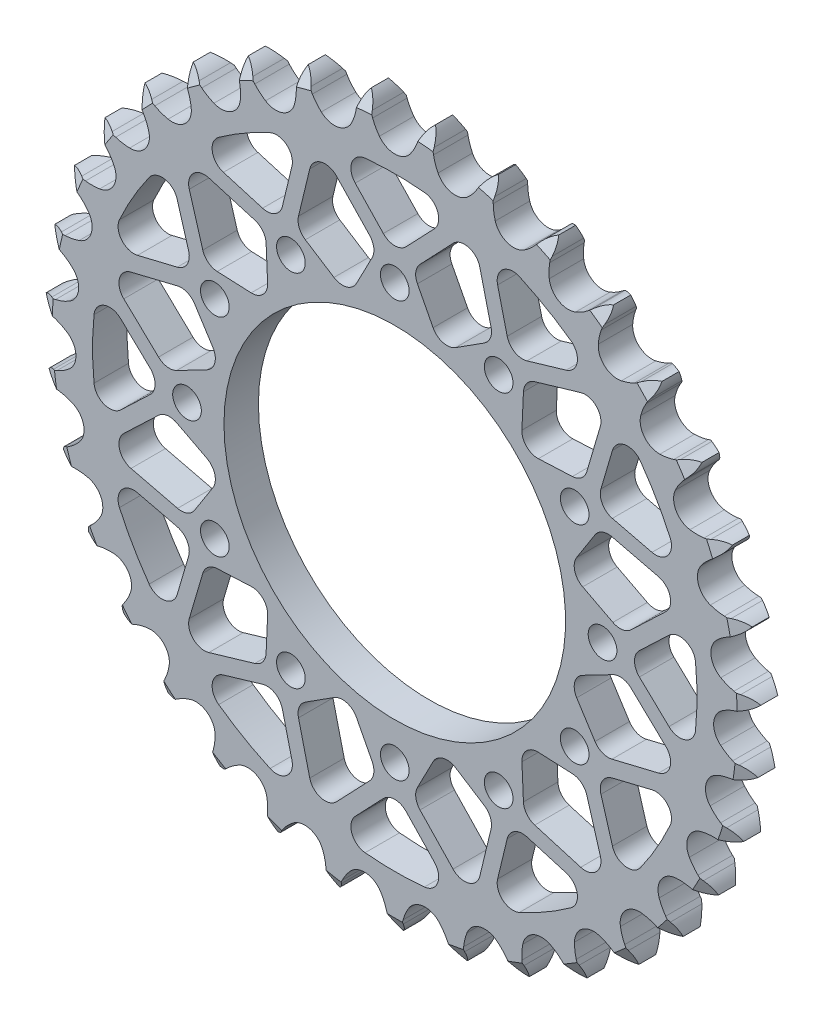
SolidWorks part; units mm, degrees
material "7075-T6 (SN)"
ref_plane "Front Plane" through (0, 0, 0) normal (0, 0, 1) x (1, 0, 0)
ref_plane "Top Plane" through (0, 0, 0) normal (0, 1, 0) x (1, 0, 0)
ref_plane "Right Plane" through (0, 0, 0) normal (1, 0, 0) x (0, 0, -1)
sketch "Work Sketch" plane through (0, 0, 0) normal (0, 0, 1) x (1, 0, 0)
  line L0 (0, 0) -> (0, 160.4542) construction
  line L1 (-112.0919, 70.8395) -> (87.2579, 70.8395) construction
  line L2 (5.0903, 120.8822) -> (5.0903, 112.9699) construction
  line L3 (-12.8497, 74.6356) -> (16.7256, 74.6356) construction
  line L4 (5.0903, 74.6356) -> (-6.074, 66.3097) construction
  line L5 (5.0903, 74.6356) -> (-4.641, 71.0332) construction
  line L6 (-4.641, 71.0332) -> (-6.9559, 77.2865)
  line L7 (-11.5114, 69.8433) -> (-7.1525, 69.8433) construction
  line L8 (-11.0678, 124.7602) -> (-11.0678, 110.2345) construction
  line L9 (0, 0) -> (-3.8324, 42.5811) construction
  circle A0 centre (0, 0) radius 70.8395
  circle A1 centre (0, 70.8395) radius 4.0088
  arc A2 (-4.641, 71.0332) -> (-3.2136, 68.4429) centre (5.0682, 74.6949) ccw
  circle A3 centre (-11.0678, 69.8433) radius 6.4401
  point P23 (-3.2136, 68.4429)
  dimension "D1" = 141.6789
  dimension "D8" = 10.3767
  dimension "D2" = 8.0177
  dimension "D3" = 5.0903
  dimension "D4" = 3.7962
  dimension "D5" = 36.714
  dimension "D6" = 16.4
  dimension "D7" = 10.3767
  dimension "D9" = 0.9961
  dimension "D10" = 11.0678
  dimension "D11" = 5.143
sketch "Teeth Sketch" plane through (0, 0, 0) normal (0, 0, 1) x (1, 0, 0)
  line L0 (5.0282, 72.0792) -> (4.641, 71.0332)
  line L1 (-8.3399, 92.6643) -> (-5.3292, 59.2127) construction
  line L2 (0, 0) -> (-12.1309, 132.2) construction
  line L3 (7.9229, 71.8186) -> (8.1171, 70.7203)
  line L4 (17927.8618, -199194.8588) -> (-17931.6941, 199237.4399) construction
  line L5 (0, 146.3285) -> (0, 56.9858) construction
  line L6 (17.8176, 70.023) -> (17.2498, 69.063)
  line L7 (0, -200000) -> (0, 200160.4542) construction
  line L8 (20.6192, 69.2498) -> (20.6142, 68.1345)
  line L9 (-4.641, 71.0332) -> (-6.9559, 77.2865) construction
  line L10 (43.6371, 57.589) -> (43.2405, 56.5465)
  line L11 (-5.0282, 72.0792) -> (-4.641, 71.0332)
  line L12 (30.0344, 65.7163) -> (29.3043, 64.873)
  line L13 (32.6529, 64.4552) -> (32.4488, 63.3587)
  line L14 (41.2858, 59.2973) -> (40.4169, 58.598)
  line L15 (51.2103, 50.9725) -> (50.2305, 50.4396)
  line L16 (53.2187, 48.8718) -> (52.6424, 47.9169)
  line L17 (59.4888, 41.0094) -> (58.4296, 40.66)
  line L18 (61.0899, 38.5838) -> (60.3523, 37.7472)
  line L19 (65.8553, 29.7283) -> (64.7507, 29.5736)
  line L20 (66.9976, 27.0558) -> (66.1224, 26.3643)
  line L21 (70.1052, 17.4916) -> (68.9907, 17.5366)
  line L22 (70.7519, 14.6581) -> (69.7673, 14.134)
  line L23 (72.1018, 4.6927) -> (71.0133, 4.9361)
  line L24 (72.2322, 1.7893) -> (71.1699, 1.4494)
  line L25 (71.781, -8.2569) -> (70.7534, -7.8232)
  line L26 (71.3909, -11.137) -> (70.2849, -11.2818)
  line L27 (69.1531, -20.9412) -> (68.2195, -20.331)
  line L28 (68.255, -23.7054) -> (67.141, -23.6503)
  line L29 (64.3026, -32.9525) -> (63.493, -32.1853)
  line L30 (62.9254, -35.5118) -> (61.8391, -35.2587)
  line L31 (57.3853, -43.9046) -> (56.7257, -43.0052)
  line L32 (55.5732, -46.1769) -> (54.5496, -45.7339)
  line L33 (48.6237, -53.4456) -> (48.1352, -52.4428)
  line L34 (46.435, -55.3578) -> (45.5069, -54.7392)
  line L35 (38.2992, -61.2688) -> (37.9976, -60.1949)
  line L36 (35.8042, -62.7594) -> (35.0015, -61.985)
  line L37 (26.7437, -67.1227) -> (26.6388, -66.0123)
  line L38 (24.0227, -68.144) -> (23.3712, -67.2387)
  line L39 (14.3287, -70.8193) -> (14.4237, -69.708)
  line L40 (11.4691, -71.3383) -> (10.9896, -70.3312)
  line L41 (1.4532, -72.2397) -> (1.7451, -71.1632)
  line L42 (-1.4532, -72.2397) -> (-1.7451, -71.1632)
  line L43 (-11.4691, -71.3383) -> (-10.9896, -70.3312)
  line L44 (-14.3287, -70.8193) -> (-14.4237, -69.708)
  line L45 (-24.0227, -68.144) -> (-23.3712, -67.2387)
  line L46 (-26.7437, -67.1227) -> (-26.6388, -66.0123)
  line L47 (-35.8042, -62.7594) -> (-35.0015, -61.985)
  line L48 (-38.2992, -61.2688) -> (-37.9976, -60.1949)
  line L49 (-46.435, -55.3578) -> (-45.5069, -54.7392)
  line L50 (-48.6237, -53.4456) -> (-48.1352, -52.4428)
  line L51 (-55.5732, -46.1769) -> (-54.5496, -45.7339)
  line L52 (-57.3853, -43.9046) -> (-56.7257, -43.0052)
  line L53 (-62.9254, -35.5118) -> (-61.8391, -35.2587)
  line L54 (-64.3026, -32.9525) -> (-63.493, -32.1853)
  line L55 (-68.255, -23.7054) -> (-67.141, -23.6503)
  line L56 (-69.1531, -20.9412) -> (-68.2195, -20.331)
  line L57 (-71.3909, -11.137) -> (-70.2849, -11.2818)
  line L58 (-71.781, -8.2569) -> (-70.7534, -7.8232)
  line L59 (-72.2322, 1.7893) -> (-71.1699, 1.4494)
  line L60 (-72.1018, 4.6927) -> (-71.0133, 4.9361)
  line L61 (-70.7519, 14.6581) -> (-69.7673, 14.134)
  line L62 (-70.1052, 17.4916) -> (-68.9907, 17.5366)
  line L63 (-66.9976, 27.0558) -> (-66.1224, 26.3643)
  line L64 (-65.8553, 29.7283) -> (-64.7507, 29.5736)
  line L65 (-61.0899, 38.5838) -> (-60.3523, 37.7472)
  line L66 (-59.4888, 41.0094) -> (-58.4296, 40.66)
  line L67 (-53.2187, 48.8718) -> (-52.6424, 47.9169)
  line L68 (-51.2103, 50.9725) -> (-50.2305, 50.4396)
  line L69 (-43.6371, 57.589) -> (-43.2405, 56.5465)
  line L70 (-41.2858, 59.2973) -> (-40.4169, 58.598)
  line L71 (-32.6529, 64.4552) -> (-32.4488, 63.3587)
  line L72 (-30.0344, 65.7163) -> (-29.3043, 64.873)
  line L73 (-20.6192, 69.2498) -> (-20.6142, 68.1345)
  line L74 (-17.8176, 70.023) -> (-17.2498, 69.063)
  line L75 (-7.9229, 71.8186) -> (-8.1171, 70.7203)
  arc A0 (-6.856, 74.7153) -> (-5.0282, 72.0792) centre (-11.0678, 69.8433) cw
  circle A1 centre (-11.0678, 69.8433) radius 6.4401 construction
  arc A2 (-3.2136, 68.4429) -> (-4.641, 71.0332) centre (5.0682, 74.6949) cw
  arc A3 (-4.641, 71.0332) -> (-3.2136, 68.4429) centre (5.0682, 74.6949) ccw construction
  circle A4 centre (0, 70.8395) radius 4.0088 construction
  arc A5 (-3.2136, 68.4429) -> (3.2136, 68.4429) centre (0, 70.8395) ccw
  arc A6 (3.2136, 68.4429) -> (4.641, 71.0332) centre (-5.0682, 74.6949) ccw
  arc A7 (6.856, 74.7153) -> (5.0282, 72.0792) centre (11.0678, 69.8433) ccw
  arc A8 (6.5951, 74.7388) -> (7.9229, 71.8186) centre (1.5811, 70.6972) cw
  arc A9 (9.059, 67.9168) -> (8.1171, 70.7203) centre (18.324, 72.5896) cw
  arc A10 (9.059, 67.9168) -> (15.3829, 66.7692) centre (12.6489, 69.701) ccw
  arc A11 (15.3829, 66.7692) -> (17.2498, 69.063) centre (8.3506, 74.3995) ccw
  arc A12 (20.0867, 72.2905) -> (17.8176, 70.023) centre (23.3609, 66.7447) ccw
  arc A13 (19.8343, 72.3601) -> (20.6192, 69.2498) centre (14.1792, 69.2787) cw
  arc A14 (21.0404, 65.2078) -> (20.6142, 68.1345) centre (30.9909, 68.1512) cw
  arc A15 (21.0404, 65.2078) -> (27.0578, 62.9494) centre (24.8912, 66.3224) ccw
  arc A16 (27.0578, 62.9494) -> (29.3043, 64.873) centre (21.5009, 71.7128) ccw
  arc A17 (32.6719, 67.5421) -> (30.0344, 65.7163) centre (34.9032, 61.5008) ccw
  arc A18 (32.4359, 67.6557) -> (32.6529, 64.4552) centre (26.3215, 65.6336) cw
  arc A19 (32.3456, 60.403) -> (32.4488, 63.3587) centre (42.6617, 61.5223) cw
  arc A20 (32.3456, 60.403) -> (37.863, 57.1065) centre (36.3335, 60.812) ccw
  arc A21 (37.863, 57.1065) -> (40.4169, 58.598) centre (33.9602, 66.7212) ccw
  arc A22 (44.207, 60.6229) -> (41.2858, 59.2973) centre (45.3237, 54.2803) ccw
  arc A23 (43.9951, 60.7768) -> (43.6371, 57.589) centre (37.6178, 59.8789) cw
  arc A24 (42.6112, 53.6567) -> (43.2405, 56.5465) centre (52.9614, 52.9161) cw
  arc A25 (42.6112, 53.6567) -> (47.4513, 49.428) centre (46.608, 53.3472) ccw
  arc A26 (47.4513, 49.428) -> (50.2305, 50.4396) centre (45.328, 59.5852) ccw
  arc A27 (54.3212, 51.7552) -> (51.2103, 50.9725) centre (54.2875, 45.3151) ccw
  arc A28 (54.1402, 51.9445) -> (53.2187, 48.8718) centre (47.7051, 52.1997) cw
  arc A29 (51.5072, 45.1859) -> (52.6424, 47.9169) centre (61.5588, 42.6091) cw
  arc A30 (51.5072, 45.1859) -> (55.5144, 40.161) centre (55.3845, 44.1677) ccw
  arc A31 (55.5144, 40.161) -> (58.4296, 40.66) centre (55.2389, 50.534) ccw
  arc A32 (62.6894, 41.224) -> (59.4888, 41.0094) centre (61.5064, 34.8935) ccw
  arc A33 (62.5452, 41.4426) -> (61.0899, 38.5838) centre (56.2591, 42.8428) cw
  arc A34 (58.7477, 35.2628) -> (60.3523, 37.7472) centre (68.1777, 30.9326) cw
  arc A35 (58.7477, 35.2628) -> (61.7933, 29.6031) centre (62.3809, 33.5686) ccw
  arc A36 (61.7933, 29.6031) -> (64.7507, 29.5736) centre (63.3744, 39.8586) ccw
  arc A37 (69.0428, 29.3679) -> (65.8553, 29.7283) centre (66.7484, 23.3503) ccw
  arc A38 (68.9399, 29.6087) -> (66.9976, 27.0558) centre (63.0048, 32.1088) cw
  arc A39 (64.1, 24.2063) -> (66.1224, 26.3643) centre (72.6052, 18.2619) cw
  arc A40 (64.1, 24.2063) -> (66.0861, 18.0937) centre (67.3723, 21.8906) ccw
  arc A41 (66.0861, 18.0937) -> (68.9907, 17.5366) centre (69.4729, 27.9021) ccw
  arc A42 (73.1771, 16.5679) -> (70.1052, 17.4916) centre (69.8451, 11.0567) ccw
  arc A43 (73.1188, 16.8232) -> (70.7519, 14.6581) centre (67.7256, 20.3429) cw
  arc A44 (67.3921, 12.3718) -> (69.7673, 14.134) centre (74.6992, 5.0042) cw
  arc A45 (67.3921, 12.3718) -> (68.2548, 6.0028) centre (70.1983, 9.509) ccw
  arc A46 (68.2548, 6.0028) -> (71.0133, 4.9361) centre (73.3386, 15.0489) ccw
  arc A47 (74.9595, 3.2354) -> (72.1018, 4.6927) centre (70.6969, -1.5923) ccw
  arc A48 (74.9477, 3.497) -> (72.2322, 1.7893) centre (70.2696, 7.9231) cw
  arc A49 (68.5181, 0.1397) -> (71.1699, 1.4494) centre (74.3923, -8.4143) cw
  arc A50 (68.5181, 0.1397) -> (68.2298, -6.281) centre (70.7681, -3.1782) ccw
  arc A51 (68.2298, -6.281) -> (70.7534, -7.8232) centre (74.8471, 1.7119) ccw
  arc A52 (74.3325, -10.2012) -> (71.781, -8.2569) centre (69.2765, -14.1901) ccw
  arc A53 (74.3677, -9.9416) -> (71.3909, -11.137) centre (70.555, -4.7513) cw
  arc A54 (67.442, -12.097) -> (70.2849, -11.2818) centre (71.6944, -21.5623) cw
  arc A55 (67.442, -12.097) -> (66.0118, -18.363) centre (69.0634, -15.7633) ccw
  arc A56 (66.0118, -18.363) -> (68.2195, -20.331) centre (73.9499, -11.6801) ccw
  arc A57 (71.3165, -23.3098) -> (69.1531, -20.9412) centre (65.6294, -26.3319) ccw
  arc A58 (71.3974, -23.0607) -> (68.255, -23.7054) centre (68.5728, -17.2731) cw
  arc A59 (64.1981, -23.9448) -> (67.141, -23.6503) centre (66.6921, -34.0173) cw
  arc A60 (64.1981, -23.9448) -> (61.6721, -29.8547) centre (65.1388, -27.8417) ccw
  arc A61 (61.6721, -29.8547) -> (63.493, -32.1853) centre (70.676, -24.6966) ccw
  arc A62 (66.0083, -35.6693) -> (64.3026, -32.9525) centre (59.873, -37.6273) ccw
  arc A63 (66.1324, -35.4386) -> (62.9254, -35.5118) centre (64.3866, -29.2396) cw
  arc A64 (58.8909, -35.023) -> (61.8391, -35.2587) centre (59.5463, -45.379) cw
  arc A65 (58.8909, -35.023) -> (55.3502, -40.3869) centre (59.1207, -39.0252) ccw
  arc A66 (55.3502, -40.3869) -> (56.7257, -43.0052) centre (65.1304, -36.9194) ccw
  arc A67 (58.5785, -46.8823) -> (57.3853, -43.9046) centre (52.1922, -47.7133) ccw
  arc A68 (58.7418, -46.6775) -> (55.5732, -46.1769) centre (58.1309, -40.2664) cw
  arc A69 (51.6909, -44.9755) -> (54.5496, -45.7339) centre (50.4867, -55.2821) cw
  arc A70 (51.6909, -44.9755) -> (47.2494, -49.6211) centre (51.2024, -48.9545) ccw
  arc A71 (47.2494, -49.6211) -> (48.1352, -52.4428) centre (57.4915, -47.9556) ccw
  arc A72 (49.266, -56.5885) -> (48.6237, -53.4456) centre (42.8339, -56.2658) ccw
  arc A73 (49.4632, -56.4161) -> (46.435, -55.3578) centre (50.0069, -49.999) cw
  arc A74 (42.8296, -53.4825) -> (45.5069, -54.7392) centre (39.8043, -63.4085) cw
  arc A75 (42.8296, -53.4825) -> (37.6299, -57.2603) centre (41.6384, -57.3103) ccw
  arc A76 (37.6299, -57.2603) -> (37.9976, -60.1949) centre (48.0048, -57.4505) ccw
  arc A77 (38.37, -64.4758) -> (38.2992, -61.2688) centre (32.0989, -63.0099) ccw
  arc A78 (38.5948, -64.3415) -> (35.8042, -62.7594) centre (40.2756, -58.1246) cw
  arc A79 (32.5916, -60.2706) -> (35.0015, -61.985) centre (27.8426, -69.4968) cw
  arc A80 (32.5916, -60.2706) -> (26.8009, -63.0592) centre (30.7361, -63.8241) ccw
  arc A81 (26.8009, -63.0592) -> (26.6388, -66.0123) centre (36.9752, -65.0988) ccw
  arc A82 (26.2407, -70.2909) -> (26.7437, -67.1227) centre (20.3322, -67.7288) ccw
  arc A83 (26.4859, -70.1989) -> (24.0227, -68.144) centre (29.2498, -64.382) cw
  arc A84 (21.3061, -65.1215) -> (23.3712, -67.2387) centre (14.9861, -73.3515) cw
  arc A85 (21.3061, -65.1215) -> (15.1105, -66.8313) centre (18.8459, -68.2866) ccw
  arc A86 (15.1105, -66.8313) -> (14.4237, -69.708) centre (24.7571, -70.6548) ccw
  arc A87 (13.2681, -73.8468) -> (14.3287, -70.8193) centre (7.912, -70.2708) ccw
  arc A88 (13.5258, -73.8) -> (11.4691, -71.3383) centre (17.2839, -68.5701) cw
  arc A89 (9.3358, -67.8793) -> (10.9896, -70.3312) centre (1.6478, -74.8485) cw
  arc A90 (9.3358, -67.8793) -> (2.9345, -68.4554) centre (6.35, -70.5543) ccw
  arc A91 (2.9345, -68.4554) -> (1.7451, -71.1632) centre (11.7434, -73.9399) ccw
  arc A92 (-0.131, -75.0291) -> (1.4532, -72.2397) centre (-4.7625, -70.5543) ccw
  arc A93 (0.131, -75.0291) -> (-1.4532, -72.2397) centre (4.7625, -70.5543) cw
  arc A94 (-2.9345, -68.4554) -> (-1.7451, -71.1632) centre (-11.7434, -73.9399) cw
  arc A95 (-2.9345, -68.4554) -> (-9.3358, -67.8793) centre (-6.35, -70.5543) ccw
  arc A96 (-9.3358, -67.8793) -> (-10.9896, -70.3312) centre (-1.6478, -74.8485) ccw
  arc A97 (-13.5258, -73.8) -> (-11.4691, -71.3383) centre (-17.2839, -68.5701) ccw
  arc A98 (-13.2681, -73.8468) -> (-14.3287, -70.8193) centre (-7.912, -70.2708) cw
  arc A99 (-15.1105, -66.8313) -> (-14.4237, -69.708) centre (-24.7571, -70.6548) cw
  arc A100 (-15.1105, -66.8313) -> (-21.3061, -65.1215) centre (-18.8459, -68.2866) ccw
  arc A101 (-21.3061, -65.1215) -> (-23.3712, -67.2387) centre (-14.9861, -73.3515) ccw
  arc A102 (-26.4859, -70.1989) -> (-24.0227, -68.144) centre (-29.2498, -64.382) ccw
  arc A103 (-26.2407, -70.2909) -> (-26.7437, -67.1227) centre (-20.3322, -67.7288) cw
  arc A104 (-26.8009, -63.0592) -> (-26.6388, -66.0123) centre (-36.9752, -65.0988) cw
  arc A105 (-26.8009, -63.0592) -> (-32.5916, -60.2706) centre (-30.7361, -63.8241) ccw
  arc A106 (-32.5916, -60.2706) -> (-35.0015, -61.985) centre (-27.8426, -69.4968) ccw
  arc A107 (-38.5948, -64.3415) -> (-35.8042, -62.7594) centre (-40.2756, -58.1246) ccw
  arc A108 (-38.37, -64.4758) -> (-38.2992, -61.2688) centre (-32.0989, -63.0099) cw
  arc A109 (-37.6299, -57.2603) -> (-37.9976, -60.1949) centre (-48.0048, -57.4505) cw
  arc A110 (-37.6299, -57.2603) -> (-42.8296, -53.4825) centre (-41.6384, -57.3103) ccw
  arc A111 (-42.8296, -53.4825) -> (-45.5069, -54.7392) centre (-39.8043, -63.4085) ccw
  arc A112 (-49.4632, -56.4161) -> (-46.435, -55.3578) centre (-50.0069, -49.999) ccw
  arc A113 (-49.266, -56.5885) -> (-48.6237, -53.4456) centre (-42.8339, -56.2658) cw
  arc A114 (-47.2494, -49.6211) -> (-48.1352, -52.4428) centre (-57.4915, -47.9556) cw
  arc A115 (-47.2494, -49.6211) -> (-51.6909, -44.9755) centre (-51.2024, -48.9545) ccw
  arc A116 (-51.6909, -44.9755) -> (-54.5496, -45.7339) centre (-50.4867, -55.2821) ccw
  arc A117 (-58.7418, -46.6775) -> (-55.5732, -46.1769) centre (-58.1309, -40.2664) ccw
  arc A118 (-58.5785, -46.8823) -> (-57.3853, -43.9046) centre (-52.1922, -47.7133) cw
  arc A119 (-55.3502, -40.3869) -> (-56.7257, -43.0052) centre (-65.1304, -36.9194) cw
  arc A120 (-55.3502, -40.3869) -> (-58.8909, -35.023) centre (-59.1207, -39.0252) ccw
  arc A121 (-58.8909, -35.023) -> (-61.8391, -35.2587) centre (-59.5463, -45.379) ccw
  arc A122 (-66.1324, -35.4386) -> (-62.9254, -35.5118) centre (-64.3866, -29.2396) ccw
  arc A123 (-66.0083, -35.6693) -> (-64.3026, -32.9525) centre (-59.873, -37.6273) cw
  arc A124 (-61.6721, -29.8547) -> (-63.493, -32.1853) centre (-70.676, -24.6966) cw
  arc A125 (-61.6721, -29.8547) -> (-64.1981, -23.9448) centre (-65.1388, -27.8417) ccw
  arc A126 (-64.1981, -23.9448) -> (-67.141, -23.6503) centre (-66.6921, -34.0173) ccw
  arc A127 (-71.3974, -23.0607) -> (-68.255, -23.7054) centre (-68.5728, -17.2731) ccw
  arc A128 (-71.3165, -23.3098) -> (-69.1531, -20.9412) centre (-65.6294, -26.3319) cw
  arc A129 (-66.0118, -18.363) -> (-68.2195, -20.331) centre (-73.9499, -11.6801) cw
  arc A130 (-66.0118, -18.363) -> (-67.442, -12.097) centre (-69.0634, -15.7633) ccw
  arc A131 (-67.442, -12.097) -> (-70.2849, -11.2818) centre (-71.6944, -21.5623) ccw
  arc A132 (-74.3677, -9.9416) -> (-71.3909, -11.137) centre (-70.555, -4.7513) ccw
  arc A133 (-74.3325, -10.2012) -> (-71.781, -8.2569) centre (-69.2765, -14.1901) cw
  arc A134 (-68.2298, -6.281) -> (-70.7534, -7.8232) centre (-74.8471, 1.7119) cw
  arc A135 (-68.2298, -6.281) -> (-68.5181, 0.1397) centre (-70.7681, -3.1782) ccw
  arc A136 (-68.5181, 0.1397) -> (-71.1699, 1.4494) centre (-74.3923, -8.4143) ccw
  arc A137 (-74.9477, 3.497) -> (-72.2322, 1.7893) centre (-70.2696, 7.9231) ccw
  arc A138 (-74.9595, 3.2354) -> (-72.1018, 4.6927) centre (-70.6969, -1.5923) cw
  arc A139 (-68.2548, 6.0028) -> (-71.0133, 4.9361) centre (-73.3386, 15.0489) cw
  arc A140 (-68.2548, 6.0028) -> (-67.3921, 12.3718) centre (-70.1983, 9.509) ccw
  arc A141 (-67.3921, 12.3718) -> (-69.7673, 14.134) centre (-74.6992, 5.0042) ccw
  arc A142 (-73.1188, 16.8232) -> (-70.7519, 14.6581) centre (-67.7256, 20.3429) ccw
  arc A143 (-73.1771, 16.5679) -> (-70.1052, 17.4916) centre (-69.8451, 11.0567) cw
  arc A144 (-66.0861, 18.0937) -> (-68.9907, 17.5366) centre (-69.4729, 27.9021) cw
  arc A145 (-66.0861, 18.0937) -> (-64.1, 24.2063) centre (-67.3723, 21.8906) ccw
  arc A146 (-64.1, 24.2063) -> (-66.1224, 26.3643) centre (-72.6052, 18.2619) ccw
  arc A147 (-68.9399, 29.6087) -> (-66.9976, 27.0558) centre (-63.0048, 32.1088) ccw
  arc A148 (-69.0428, 29.3679) -> (-65.8553, 29.7283) centre (-66.7484, 23.3503) cw
  arc A149 (-61.7933, 29.6031) -> (-64.7507, 29.5736) centre (-63.3744, 39.8586) cw
  arc A150 (-61.7933, 29.6031) -> (-58.7477, 35.2628) centre (-62.3809, 33.5686) ccw
  arc A151 (-58.7477, 35.2628) -> (-60.3523, 37.7472) centre (-68.1777, 30.9326) ccw
  arc A152 (-62.5452, 41.4426) -> (-61.0899, 38.5838) centre (-56.2591, 42.8428) ccw
  arc A153 (-62.6894, 41.224) -> (-59.4888, 41.0094) centre (-61.5064, 34.8935) cw
  arc A154 (-55.5144, 40.161) -> (-58.4296, 40.66) centre (-55.2389, 50.534) cw
  arc A155 (-55.5144, 40.161) -> (-51.5072, 45.1859) centre (-55.3845, 44.1677) ccw
  arc A156 (-51.5072, 45.1859) -> (-52.6424, 47.9169) centre (-61.5588, 42.6091) ccw
  arc A157 (-54.1402, 51.9445) -> (-53.2187, 48.8718) centre (-47.7051, 52.1997) ccw
  arc A158 (-54.3212, 51.7552) -> (-51.2103, 50.9725) centre (-54.2875, 45.3151) cw
  arc A159 (-47.4513, 49.428) -> (-50.2305, 50.4396) centre (-45.328, 59.5852) cw
  arc A160 (-47.4513, 49.428) -> (-42.6112, 53.6567) centre (-46.608, 53.3472) ccw
  arc A161 (-42.6112, 53.6567) -> (-43.2405, 56.5465) centre (-52.9614, 52.9161) ccw
  arc A162 (-43.9951, 60.7768) -> (-43.6371, 57.589) centre (-37.6178, 59.8789) ccw
  arc A163 (-44.207, 60.6229) -> (-41.2858, 59.2973) centre (-45.3237, 54.2803) cw
  arc A164 (-37.863, 57.1065) -> (-40.4169, 58.598) centre (-33.9602, 66.7212) cw
  arc A165 (-37.863, 57.1065) -> (-32.3456, 60.403) centre (-36.3335, 60.812) ccw
  arc A166 (-32.3456, 60.403) -> (-32.4488, 63.3587) centre (-42.6617, 61.5223) ccw
  arc A167 (-32.4359, 67.6557) -> (-32.6529, 64.4552) centre (-26.3215, 65.6336) ccw
  arc A168 (-32.6719, 67.5421) -> (-30.0344, 65.7163) centre (-34.9032, 61.5008) cw
  arc A169 (-27.0578, 62.9494) -> (-29.3043, 64.873) centre (-21.5009, 71.7128) cw
  arc A170 (-27.0578, 62.9494) -> (-21.0404, 65.2078) centre (-24.8912, 66.3224) ccw
  arc A171 (-21.0404, 65.2078) -> (-20.6142, 68.1345) centre (-30.9909, 68.1512) ccw
  arc A172 (-19.8343, 72.3601) -> (-20.6192, 69.2498) centre (-14.1792, 69.2787) ccw
  arc A173 (-20.0867, 72.2905) -> (-17.8176, 70.023) centre (-23.3609, 66.7447) cw
  arc A174 (-15.3829, 66.7692) -> (-17.2498, 69.063) centre (-8.3506, 74.3995) cw
  arc A175 (-15.3829, 66.7692) -> (-9.059, 67.9168) centre (-12.6489, 69.701) ccw
  arc A176 (-9.059, 67.9168) -> (-8.1171, 70.7203) centre (-18.324, 72.5896) ccw
  arc A177 (-6.5951, 74.7388) -> (-7.9229, 71.8186) centre (-1.5811, 70.6972) ccw
  point P77 (0, 0)
  dimension "D1" = 5.143
  dimension "D2" = 5.243
  dimension "D3" = 35
extrude "Extrusion" add sketch "Teeth Sketch" along normal blind 7.2136 contours A0 region at (0, 0, 0)
sketch "Sketch1" plane through (0, 0, 0) normal (0, 0, -1) x (-1, 0, 0)
  circle A0 centre (0, 0) radius 78.9443
  circle A1 centre (0, 0) radius 35.7643
  dimension "D1" = 43.18
extrude "Cut-Extrude" cut sketch "Sketch1" against normal through all both and the other way through all contours A1
ref_axis "Axis2" through (0, 0, -0.3607) along (0, 0, 1)
ref_axis "Axis1" [suppressed] through (0, 0, 7.2136) along (0, 0, -1)
ref_plane "Sprocket Center Plane" through (0, 0, 3.6068) normal (0, 0, 1) x (1, 0, 0)
sketch "Pitch Circle" plane through (0, 0, 3.6068) normal (0, 0, -1) x (-1, 0, 0)
  circle A0 centre (0, 0) radius 82.9531 construction
  dimension "D1" = 165.9063
sketch "Chain Pitch Circle" plane through (0, 0, 0) normal (0, 0, -1) x (-1, 0, 0)
  circle A0 centre (0, 0) radius 82.9531 construction
  dimension "D1" = 165.9063
ref_plane "Center Plane" through (0, 0, 3.6068) normal (0, 0, 1) x (1, 0, 0)
hole_wizard "Ø6.0mm Dowel Hole1" positions "Sketch7" profile "Sketch8" hole size "Ø6.0" standard "ANSI Metric" end condition through all
sketch "Sketch7" plane through (0, 0, 7.2136) normal (0, 0, 1) x (1, 0, 0)
  point P0 (-43.5, 0)
  dimension "D1" = 43.5
sketch "Sketch8" plane through (-43.5, 0, 7.2136) normal (1, 0, 0) x (0, -1, 0)
  line L0 (0, 0) -> (0, 7.2136)
  line L1 (0, 7.2136) -> (3, 7.2136)
  line L2 (3, 7.2136) -> (3, 0)
  line L5 (3, 0) -> (0, 0)
  line L11 (0, -6.35) -> (0, 107.95) construction
  dimension "Thru Hole Dia." = 6
  dimension "Thru Hole Depth" = 7.2136
pattern_circular "CirPattern1" count 12 over 360 about axis through (0, 0, 7.2136) along (0, 0, -1) of "Ø6.0mm Dowel Hole1" reverse direction yes
ref_plane "Plane1" through (0, 0, 3.6068) normal (0, 0, -1) x (-1, 0, 0)
sketch "Sketch9" plane through (0, 0, 0) normal (0, 0, 1) x (1, 0, 0)
  line L0 (-43.5, 0) -> (-63.2746, 0) construction
  line L1 (-61.9966, 12.6533) -> (-48.707, 0)
  line L2 (-61.9966, -12.6533) -> (-48.707, 0)
  line L11 (-43.5, 0) -> (-37.6721, 21.75) construction
  line L13 (-61.1186, 16.3767) -> (-36.1404, 9.6838) construction
  line L18 (-43.1887, 20.7127) -> (-36.1404, 9.6838)
  line L19 (-47.7589, 3.6566) -> (-36.1404, 9.6838)
  line L20 (-43.1887, 20.7127) -> (-61.1186, 16.3767)
  line L21 (-47.7589, 3.6566) -> (-61.1186, 16.3767)
  circle A0 centre (0, 0) radius 66.8306 construction
  arc A1 (-15.3829, 66.7692) -> (-9.059, 67.9168) centre (-12.6489, 69.701) ccw construction
  circle A2 centre (-43.5, 0) radius 3 construction
  circle A3 centre (-43.5, 0) radius 5.207
  circle A4 centre (-37.6721, 21.75) radius 3 construction
  circle A6 centre (-37.6721, 21.75) radius 5.207
  circle A196 centre (0, 0) radius 63.2746
  circle A197 centre (0, 0) radius 35.7643 construction
  circle A198 centre (0, 0) radius 35.7643
  circle A199 centre (0, 0) radius 37.4153 construction
  point P17 (-40.5861, 10.875)
  dimension "D1" = 3.556
  dimension "D2" = 1.651
  dimension "D3" = 10.414
  dimension "D4" = 3.302
extrude "Cut-Extrude2" cut sketch "Sketch9" along normal through all contours L1 A196 L2 | L21 L19 L18 L20 region at (-58.1293, 0, 0) region at (-47.5776, 12.7484, 0)
fillet "Fillet2" radius 3.302 7 edges at (-61.1186, 16.3767, 3.6068) (-36.1404, 9.6838, 3.6068) (-47.7589, 3.6566, 3.6068) (-43.1887, 20.7127, 3.6068) (-61.9966, -12.6533, 3.6068) (-48.707, 0, 3.6068) (-61.9966, 12.6533, 3.6068)
pattern_circular "CirPattern3" count 12 over 360 about axis through (0, 0, 7.2136) along (0, 0, -1) of "Cut-Extrude2", "Fillet2"
sketch "Sketch14" plane through (0, 0, 7.2136) normal (0, 0, 1) x (1, 0, 0)
  line L0 (-45.6677, -4.7414) -> (-39.3483, -8.0197) construction
  line L1 (-38.2956, 5.9905) -> (-37.9766, 6.1559)
  line L2 (-43.5, 0) -> (-38.293, 0) construction
  line L3 (-38.2956, -5.9905) -> (-37.9766, -6.1559)
  line L4 (-30.1697, 24.3357) -> (-29.8108, 24.3195)
  line L5 (-36.1602, 13.9599) -> (-35.9667, 13.6571)
  line L6 (-13.9599, 36.1602) -> (-13.6571, 35.9667)
  line L7 (-24.3357, 30.1697) -> (-24.3195, 29.8108)
  line L8 (5.9905, 38.2956) -> (6.1559, 37.9766)
  line L9 (-5.9905, 38.2956) -> (-6.1559, 37.9766)
  line L10 (24.3357, 30.1697) -> (24.3195, 29.8108)
  line L11 (13.9599, 36.1602) -> (13.6571, 35.9667)
  line L12 (36.1602, 13.9599) -> (35.9667, 13.6571)
  line L13 (30.1697, 24.3357) -> (29.8108, 24.3195)
  line L14 (38.2956, -5.9905) -> (37.9766, -6.1559)
  line L15 (38.2956, 5.9905) -> (37.9766, 6.1559)
  line L16 (30.1697, -24.3357) -> (29.8108, -24.3195)
  line L17 (36.1602, -13.9599) -> (35.9667, -13.6571)
  line L18 (13.9599, -36.1602) -> (13.6571, -35.9667)
  line L19 (24.3357, -30.1697) -> (24.3195, -29.8108)
  line L20 (-5.9905, -38.2956) -> (-6.1559, -37.9766)
  line L21 (5.9905, -38.2956) -> (6.1559, -37.9766)
  line L22 (-24.3357, -30.1697) -> (-24.3195, -29.8108)
  line L23 (-13.9599, -36.1602) -> (-13.6571, -35.9667)
  line L24 (-36.1602, -13.9599) -> (-35.9667, -13.6571)
  line L25 (-30.1697, -24.3357) -> (-29.8108, -24.3195)
  arc A0 (-39.0014, -2.6222) -> (-39.0014, 2.6222) centre (-43.5, 0) ccw
  circle A1 centre (0, 0) radius 35.7643 construction
  arc A2 (-37.9766, -6.1559) -> (-39.0014, -2.6222) centre (-36.807, -3.9013) cw
  arc A3 (-38.2956, 5.9905) -> (-36.1602, 13.9599) centre (-40.8688, 10.9508) ccw
  arc A4 (-38.2956, 5.9905) -> (-36.1602, 13.9599) centre (-40.8688, 10.9508) ccw
  arc A5 (-37.9766, 6.1559) -> (-39.0014, 2.6222) centre (-36.807, 3.9013) ccw
  circle A6 centre (0, 0) radius 35.7643
  arc A7 (-30.1697, 24.3357) -> (-24.3357, 30.1697) centre (-29.918, 29.918) ccw
  arc A8 (-29.8108, 24.3195) -> (-32.4651, 21.7716) centre (-29.9252, 21.7821) ccw
  arc A9 (-35.0873, 17.2299) -> (-32.4651, 21.7716) centre (-37.6721, 21.75) ccw
  arc A10 (-35.9667, 13.6571) -> (-35.0873, 17.2299) centre (-33.8264, 15.0249) cw
  arc A11 (-13.9599, 36.1602) -> (-5.9905, 38.2956) centre (-10.9508, 40.8688) ccw
  arc A12 (-13.6571, 35.9667) -> (-17.2299, 35.0873) centre (-15.0249, 33.8264) ccw
  arc A13 (-21.7716, 32.4651) -> (-17.2299, 35.0873) centre (-21.75, 37.6721) ccw
  arc A14 (-24.3195, 29.8108) -> (-21.7716, 32.4651) centre (-21.7821, 29.9252) cw
  arc A15 (5.9905, 38.2956) -> (13.9599, 36.1602) centre (10.9508, 40.8688) ccw
  arc A16 (6.1559, 37.9766) -> (2.6222, 39.0014) centre (3.9013, 36.807) ccw
  arc A17 (-2.6222, 39.0014) -> (2.6222, 39.0014) centre (0, 43.5) ccw
  arc A18 (-6.1559, 37.9766) -> (-2.6222, 39.0014) centre (-3.9013, 36.807) cw
  arc A19 (24.3357, 30.1697) -> (30.1697, 24.3357) centre (29.918, 29.918) ccw
  arc A20 (24.3195, 29.8108) -> (21.7716, 32.4651) centre (21.7821, 29.9252) ccw
  arc A21 (17.2299, 35.0873) -> (21.7716, 32.4651) centre (21.75, 37.6721) ccw
  arc A22 (13.6571, 35.9667) -> (17.2299, 35.0873) centre (15.0249, 33.8264) cw
  arc A23 (36.1602, 13.9599) -> (38.2956, 5.9905) centre (40.8688, 10.9508) ccw
  arc A24 (35.9667, 13.6571) -> (35.0873, 17.2299) centre (33.8264, 15.0249) ccw
  arc A25 (32.4651, 21.7716) -> (35.0873, 17.2299) centre (37.6721, 21.75) ccw
  arc A26 (29.8108, 24.3195) -> (32.4651, 21.7716) centre (29.9252, 21.7821) cw
  arc A27 (38.2956, -5.9905) -> (36.1602, -13.9599) centre (40.8688, -10.9508) ccw
  arc A28 (37.9766, -6.1559) -> (39.0014, -2.6222) centre (36.807, -3.9013) ccw
  arc A29 (39.0014, 2.6222) -> (39.0014, -2.6222) centre (43.5, 0) ccw
  arc A30 (37.9766, 6.1559) -> (39.0014, 2.6222) centre (36.807, 3.9013) cw
  arc A31 (30.1697, -24.3357) -> (24.3357, -30.1697) centre (29.918, -29.918) ccw
  arc A32 (29.8108, -24.3195) -> (32.4651, -21.7716) centre (29.9252, -21.7821) ccw
  arc A33 (35.0873, -17.2299) -> (32.4651, -21.7716) centre (37.6721, -21.75) ccw
  arc A34 (35.9667, -13.6571) -> (35.0873, -17.2299) centre (33.8264, -15.0249) cw
  arc A35 (13.9599, -36.1602) -> (5.9905, -38.2956) centre (10.9508, -40.8688) ccw
  arc A36 (13.6571, -35.9667) -> (17.2299, -35.0873) centre (15.0249, -33.8264) ccw
  arc A37 (21.7716, -32.4651) -> (17.2299, -35.0873) centre (21.75, -37.6721) ccw
  arc A38 (24.3195, -29.8108) -> (21.7716, -32.4651) centre (21.7821, -29.9252) cw
  arc A39 (-5.9905, -38.2956) -> (-13.9599, -36.1602) centre (-10.9508, -40.8688) ccw
  arc A40 (-6.1559, -37.9766) -> (-2.6222, -39.0014) centre (-3.9013, -36.807) ccw
  arc A41 (2.6222, -39.0014) -> (-2.6222, -39.0014) centre (0, -43.5) ccw
  arc A42 (6.1559, -37.9766) -> (2.6222, -39.0014) centre (3.9013, -36.807) cw
  arc A43 (-24.3357, -30.1697) -> (-30.1697, -24.3357) centre (-29.918, -29.918) ccw
  arc A44 (-24.3195, -29.8108) -> (-21.7716, -32.4651) centre (-21.7821, -29.9252) ccw
  arc A45 (-17.2299, -35.0873) -> (-21.7716, -32.4651) centre (-21.75, -37.6721) ccw
  arc A46 (-13.6571, -35.9667) -> (-17.2299, -35.0873) centre (-15.0249, -33.8264) cw
  arc A47 (-36.1602, -13.9599) -> (-38.2956, -5.9905) centre (-40.8688, -10.9508) ccw
  arc A48 (-35.9667, -13.6571) -> (-35.0873, -17.2299) centre (-33.8264, -15.0249) ccw
  arc A49 (-32.4651, -21.7716) -> (-35.0873, -17.2299) centre (-37.6721, -21.75) ccw
  arc A50 (-29.8108, -24.3195) -> (-32.4651, -21.7716) centre (-29.9252, -21.7821) cw
  point P10 (-41.0188, -4.5778)
  point P16 (-41.0188, 4.5778)
  point P144 (0, 0)
  dimension "D2" = 2.54
  dimension "D1" = 2.286
  dimension "D3" = 12
extrude "Cut-Extrude7" [suppressed] cut sketch "Sketch14" against normal through all
sketch "Sketch15" plane through (0, 0, 0) normal (0, 0, -1) x (-1, 0, 0)
  line L9 (-30.8009, 49.3753) -> (-28.037, 48.5615)
  line L10 (-28.037, 48.5615) -> (-27.3598, 51.362)
  line L11 (-48.5615, 28.037) -> (-49.3753, 30.8009)
  line L12 (-51.362, 27.3598) -> (-48.5615, 28.037)
  line L13 (-48.5615, 28.037) -> (-49.3753, 30.8009)
  line L14 (-51.362, 27.3598) -> (-48.5615, 28.037)
  line L15 (-46.8809, 9.8349) -> (-43.4148, 11.633)
  line L16 (-50.8663, 13.6296) -> (-46.8809, 9.8349)
  line L17 (-45.5175, 14.9231) -> (-50.8663, 13.6296)
  line L18 (-43.4148, 11.633) -> (-45.5175, 14.9231)
  line L19 (-46.8809, 9.8349) -> (-43.4148, 11.633)
  line L20 (-50.8663, 13.6296) -> (-46.8809, 9.8349)
  line L21 (-45.5175, 14.9231) -> (-50.8663, 13.6296)
  line L22 (-43.4148, 11.633) -> (-45.5175, 14.9231)
  line L23 (-37.2367, 37.2367) -> (-35.6825, 31.9577)
  line L24 (-35.6825, 31.9577) -> (-31.7819, 31.7819)
  line L25 (-31.7819, 31.7819) -> (-31.9577, 35.6825)
  line L26 (-31.9577, 35.6825) -> (-37.2367, 37.2367)
  line L27 (-1.9867, 58.1607) -> (0, 56.074)
  line L28 (0, 56.074) -> (1.9867, 58.1607)
  line L29 (-13.6296, 50.8663) -> (-14.9231, 45.5175)
  line L30 (-14.9231, 45.5175) -> (-11.633, 43.4148)
  line L31 (-11.633, 43.4148) -> (-9.8349, 46.8809)
  line L32 (-9.8349, 46.8809) -> (-13.6296, 50.8663)
  line L33 (27.3598, 51.362) -> (28.037, 48.5615)
  line L34 (28.037, 48.5615) -> (30.8009, 49.3753)
  line L35 (13.6296, 50.8663) -> (9.8349, 46.8809)
  line L36 (9.8349, 46.8809) -> (11.633, 43.4148)
  line L37 (11.633, 43.4148) -> (14.9231, 45.5175)
  line L38 (14.9231, 45.5175) -> (13.6296, 50.8663)
  line L39 (49.3753, 30.8009) -> (48.5615, 28.037)
  line L40 (48.5615, 28.037) -> (51.362, 27.3598)
  line L41 (37.2367, 37.2367) -> (31.9577, 35.6825)
  line L42 (31.9577, 35.6825) -> (31.7819, 31.7819)
  line L43 (31.7819, 31.7819) -> (35.6825, 31.9577)
  line L44 (35.6825, 31.9577) -> (37.2367, 37.2367)
  line L45 (58.1607, 1.9867) -> (56.074, 0)
  line L46 (56.074, 0) -> (58.1607, -1.9867)
  line L47 (50.8663, 13.6296) -> (45.5175, 14.9231)
  line L48 (45.5175, 14.9231) -> (43.4148, 11.633)
  line L49 (43.4148, 11.633) -> (46.8809, 9.8349)
  line L50 (46.8809, 9.8349) -> (50.8663, 13.6296)
  line L51 (51.362, -27.3598) -> (48.5615, -28.037)
  line L52 (48.5615, -28.037) -> (49.3753, -30.8009)
  line L53 (50.8663, -13.6296) -> (46.8809, -9.8349)
  line L54 (46.8809, -9.8349) -> (43.4148, -11.633)
  line L55 (43.4148, -11.633) -> (45.5175, -14.9231)
  line L56 (45.5175, -14.9231) -> (50.8663, -13.6296)
  line L57 (30.8009, -49.3753) -> (28.037, -48.5615)
  line L58 (28.037, -48.5615) -> (27.3598, -51.362)
  line L59 (37.2367, -37.2367) -> (35.6825, -31.9577)
  line L60 (35.6825, -31.9577) -> (31.7819, -31.7819)
  line L61 (31.7819, -31.7819) -> (31.9577, -35.6825)
  line L62 (31.9577, -35.6825) -> (37.2367, -37.2367)
  line L63 (1.9867, -58.1607) -> (0, -56.074)
  line L64 (0, -56.074) -> (-1.9867, -58.1607)
  line L65 (13.6296, -50.8663) -> (14.9231, -45.5175)
  line L66 (14.9231, -45.5175) -> (11.633, -43.4148)
  line L67 (11.633, -43.4148) -> (9.8349, -46.8809)
  line L68 (9.8349, -46.8809) -> (13.6296, -50.8663)
  line L69 (-27.3598, -51.362) -> (-28.037, -48.5615)
  line L70 (-28.037, -48.5615) -> (-30.8009, -49.3753)
  line L71 (-13.6296, -50.8663) -> (-9.8349, -46.8809)
  line L72 (-9.8349, -46.8809) -> (-11.633, -43.4148)
  line L73 (-11.633, -43.4148) -> (-14.9231, -45.5175)
  line L74 (-14.9231, -45.5175) -> (-13.6296, -50.8663)
  line L75 (-49.3753, -30.8009) -> (-48.5615, -28.037)
  line L76 (-48.5615, -28.037) -> (-51.362, -27.3598)
  line L77 (-37.2367, -37.2367) -> (-31.9577, -35.6825)
  line L78 (-31.9577, -35.6825) -> (-31.7819, -31.7819)
  line L79 (-31.7819, -31.7819) -> (-35.6825, -31.9577)
  line L80 (-35.6825, -31.9577) -> (-37.2367, -37.2367)
  line L81 (-58.1607, -1.9867) -> (-56.074, 0)
  line L82 (-56.074, 0) -> (-58.1607, 1.9867)
  line L83 (-50.8663, -13.6296) -> (-45.5175, -14.9231)
  line L84 (-45.5175, -14.9231) -> (-43.4148, -11.633)
  line L85 (-43.4148, -11.633) -> (-46.8809, -9.8349)
  line L86 (-46.8809, -9.8349) -> (-50.8663, -13.6296)
  circle A13 centre (0, 0) radius 31.6425
  arc A18 (-27.3598, 51.362) -> (-30.8009, 49.3753) centre (0, 0) ccw
  arc A19 (1.9867, 58.1607) -> (-1.9867, 58.1607) centre (0, 0) ccw
  arc A20 (30.8009, 49.3753) -> (27.3598, 51.362) centre (0, 0) ccw
  arc A21 (51.362, 27.3598) -> (49.3753, 30.8009) centre (0, 0) ccw
  arc A22 (-49.3753, 30.8009) -> (-51.362, 27.3598) centre (0, 0) ccw
  arc A23 (-49.3753, 30.8009) -> (-51.362, 27.3598) centre (0, 0) ccw
  arc A24 (58.1607, -1.9867) -> (58.1607, 1.9867) centre (0, 0) ccw
  arc A25 (49.3753, -30.8009) -> (51.362, -27.3598) centre (0, 0) ccw
  arc A26 (27.3598, -51.362) -> (30.8009, -49.3753) centre (0, 0) ccw
  arc A27 (-1.9867, -58.1607) -> (1.9867, -58.1607) centre (0, 0) ccw
  arc A28 (-30.8009, -49.3753) -> (-27.3598, -51.362) centre (0, 0) ccw
  arc A29 (-51.362, -27.3598) -> (-49.3753, -30.8009) centre (0, 0) ccw
  arc A30 (-58.1607, 1.9867) -> (-58.1607, -1.9867) centre (0, 0) ccw
  point P3 (0, 0)
  point P28 (0, 0)
  point P123 (0, 0)
  dimension "D6" = 5.08
  dimension "D7" = 5.08
  dimension "D8" = 12
sketch "Sketch16" plane through (0, 0, 0) normal (0, 0, -1) x (-1, 0, 0)
  line L1 (88.9, 88.9) -> (-88.9, 88.9)
  line L2 (88.9, 88.9) -> (88.9, -88.9)
  line L3 (88.9, -88.9) -> (-88.9, -88.9)
  line L4 (-88.9, 88.9) -> (-88.9, -88.9)
  line L5 (88.9, 88.9) -> (-88.9, -88.9) construction
  line L6 (88.9, -88.9) -> (-88.9, 88.9) construction
  point P0 (0, 0)
  dimension "D1" = 177.8
  dimension "D2" = 177.8
sketch "Sketch17" plane through (0, 0, 0) normal (0, 0, -1) x (-1, 0, 0)
  line L0 (88.9, 88.9) -> (-88.9, -88.9) construction
  line L2 (88.9, -88.9) -> (-88.9, -88.9)
  line L3 (88.9, -88.9) -> (88.9, 88.9)
  line L4 (88.9, 88.9) -> (-88.9, 88.9)
  line L5 (-88.9, -88.9) -> (-88.9, 88.9)
  line L6 (88.9, -88.9) -> (-88.9, 88.9) construction
  line L7 (88.9, 88.9) -> (-88.9, -88.9) construction
  circle A0 centre (0, 0) radius 74.8895
sketch "Sketch18" plane through (0, 0, 0) normal (1, 0, 0) x (0, 0, -1)
  line L0 (-4.4369, -78.3168) -> (-5.3848, -74.8895)
  line L1 (-5.3848, -74.8895) -> (-5.3848, -71.6959)
  line L2 (-5.3848, -71.6959) -> (-7.2136, -71.6959)
  line L3 (-7.2136, -71.6959) -> (-5.3848, -74.8895)
  line L4 (-7.2136, -71.6959) -> (-7.2136, -74.8895)
  line L5 (-7.2136, -74.8895) -> (-5.3848, -74.8895)
  line L6 (-7.2136, -71.6959) -> (-7.2136, -74.8895)
  line L7 (-5.3848, -74.8895) -> (-7.2136, -71.6959)
  point P5 (0, 0)
  dimension "D1" = 3.556
  dimension "D2" = 3.1936
  dimension "D3" = 1.8288
revolve "Cut-Revolve2" cut sketch "Sketch18" angle 360 about axis through (0, 0, -0.3607) along (0, 0, 1) region at (0, -73.825, 6.604)
mirror "Mirror1" about plane through (0, 0, 3.6068) normal (0, 0, -1) of "Cut-Revolve2"
equation "\"P\"= 0.500'//Chain Pitch"
equation "\"N\" = 35'//Number of Teeth"
equation "\"Dr\"= 5 / 16'//Roller Diameter"
equation "\"Ds\"= 1.0005 * \"Dr\" + 0.003'Seating Curve DIameter"
equation "\"R\"= \"Ds\" / 2"
equation "\"A\"= 35 + 60 / \"N\""
equation "\"B\"= 18 - 56 / \"N\""
equation "\"ac\"= 0.8 * \"Dr\""
equation "\"M\"= 0.8 * \"Dr\" * cos ( 35 + 60 / \"N\" )"
equation "\"T\"= 0.8 * \"Dr\" * sin ( 35 + 60 / \"N\" )"
equation "\"E\"= 1.3025 * \"Dr\" + 0.0015"
equation "\"Chordal Length of Arc xy\"= ( 2.605 * \"Dr\" + 0.003 ) * sin ( 9 - 28 / \"N\" )"
equation "\"yz\"= \"Dr\" * ( 1.4 * sin ( 17 - 64 / \"N\" ) - 0.8 * sin ( 18 - 56 / \"N\" ) )"
equation "\"ab\"= 1.4 * \"Dr\""
equation "\"W\"= 1.4 * \"Dr\" * cos ( 180 / \"N\" )"
equation "\"V\"= 1.4 * \"Dr\" * sin ( 180 / \"N\" )"
equation "\"F\"= \"Dr\" * ( 0.8 * cos ( 18 - 56 / \"N\" ) + 1.4 * cos ( 17 - 64 / \"N\" ) - 1.3025 )"
equation "\"H\"= sqr ( \"F\" ^ 2 - ( 1.4 * \"Dr\" - \"P\" / 2 ) ^ 2 )"
equation "\"S\"= \"P\" / 2 * cos ( 180 / \"N\" ) + \"H\" * sin ( 180 / \"N\" )"
equation "\"PD\"= \"P\" / ( sin ( 180 / \"N\" ) )"
equation "\"D1@Work Sketch\" = \"PD\""
equation "\"D3@Work Sketch\" = \"M\""
equation "\"D4@Work Sketch\" = \"T\""
equation "\"D5@Work Sketch\" = \"A\""
equation "\"D6@Work Sketch\" = \"B\""
equation "\"D7@Work Sketch\" = \"E\""
equation "\"D8@Work Sketch\" = \"E\""
equation "\"D9@Work Sketch\" = \"V\""
equation "\"D10@Work Sketch\" = \"W\""
equation "\"D2@Work Sketch\" = \"R\" * 2"
equation "\"D11@Work Sketch\" = 180 / \"N\""
equation "\"D2@Teeth Sketch\" = 180 / \"N\" + 0.1"
equation "\"D3@Teeth Sketch\" = \"N\""
equation "\"Edge Thickness\"=1.7"
equation "\"D1@Sketch1\"=\"Edge Thickness\""
equation "\"InnerRib\"=0.060000"
equation "\"ST\"= 0.284'//Sprocket Thickness"
